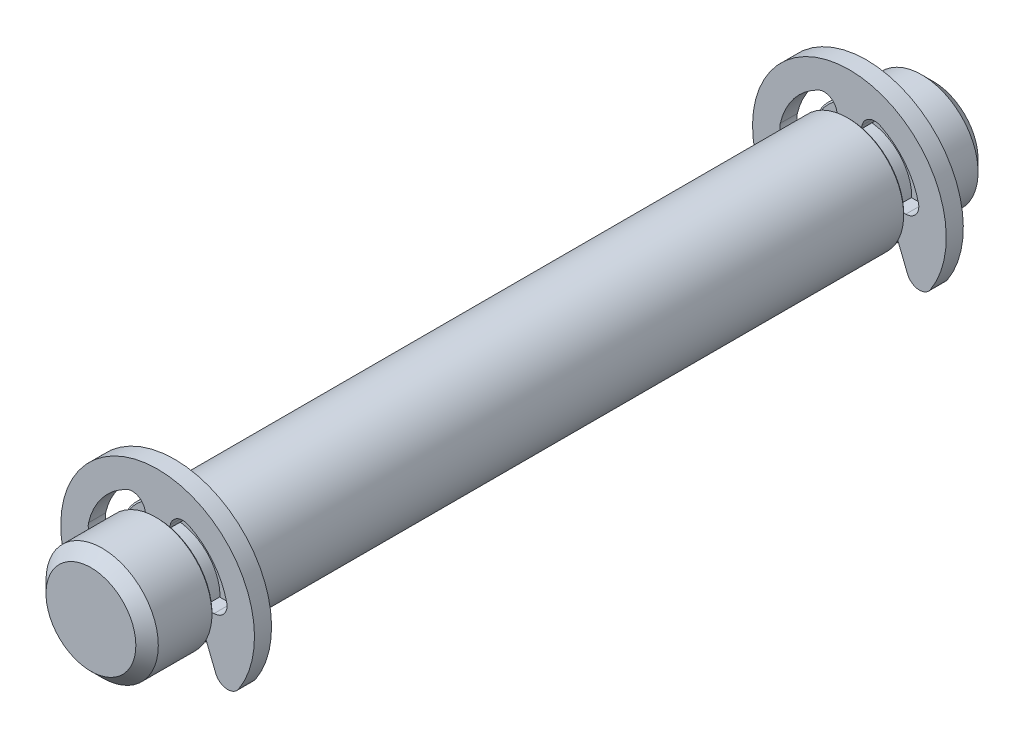
SolidWorks part; units mm, degrees
material "Plain Carbon Steel"
ref_plane "Front" through (0, 0, 0) normal (0, 0, 1) x (1, 0, 0)
ref_plane "Top" through (0, 0, 0) normal (0, 1, 0) x (1, 0, 0)
ref_plane "Right" through (0, 0, 0) normal (1, 0, 0) x (0, 0, -1)
sketch "Sketch0" plane through (0, 0, 0) normal (0, 1, 0) x (1, 0, 0)
  line L0 (0, 12) -> (0, -12) construction
  line L1 (0, -15) -> (0, 15) construction
  line L2 (-2, 0) -> (2, 0) construction
  line L3 (-1.6, 12) -> (1.6, 12) construction
  line L4 (-1.6, 12.64) -> (1.6, 12.64) construction
  point P3 (0, 0)
  point P12 (0, 0)
  point P14 (0, 12)
  point P17 (0, 0)
  point P20 (0, 12.64)
  dimension "Usable_L" = 24
  dimension "OA_L" = 30
  dimension "Pin_OD" = 4
  dimension "Groove_OD" = 3.2
  dimension "Groove_W" = 0.64
sketch "Sketch1" plane through (0, 0, 0) normal (0, 1, 0) x (1, 0, 0)
  line L1 (-2, 12) -> (-1.6, 12)
  line L2 (-1.6, 12) -> (-1.6, 12.64)
  line L3 (-1.6, 12.64) -> (-2, 12.64)
  line L4 (-2, 12.64) -> (-2, 15)
  line L5 (-2, 15) -> (0, 15)
  line L9 (-2, 0) -> (2, 0) construction
  line L10 (0, 15) -> (0, -15)
  line L11 (-2, -15) -> (0, -15)
  line L12 (-2, -12.64) -> (-2, -15)
  line L13 (-1.6, -12.64) -> (-2, -12.64)
  line L14 (-1.6, -12) -> (-1.6, -12.64)
  line L15 (-2, -12) -> (-1.6, -12)
  line L16 (-2, -12) -> (-2, 12)
revolve "Revolve1" add sketch "Sketch1" angle 360 about L10
chamfer "Chamfer1" distance 0.4 angle 45 2 edges at (-2, 0, -15) (-2, 0, 15)
ref_plane "Plane1" through (0, 0, 12.32) normal (0, 0, 1) x (1, 0, 0)
sketch "Sketch2" plane through (0, 0, 12.32) normal (0, 0, 1) x (1, 0, 0)
  line L14 (-2.3509, -2.525) -> (2.3509, -2.525) construction
  line L15 (0, 1.6) -> (0, 3.45) construction
  line L18 (-2.3509, -2.525) -> (-1.5317, -0.4625)
  line L19 (2.3509, -2.525) -> (1.5317, -0.4625)
  line L24 (1.6, 0) -> (2.525, 0) construction
  line L25 (-1.6, 0) -> (-2.0625, 0) construction
  line L26 (-2.0625, 0) -> (-2.525, 0) construction
  line L27 (0, 0) -> (0, -0.4625) construction
  line L28 (-1.5317, -0.4625) -> (1.5317, -0.4625) construction
  line L29 (-1.6, 0) -> (-2.525, 0)
  line L30 (0, 2.525) -> (0, 1.6) construction
  line L31 (-0.4507, 1.9588) -> (-0.5662, 2.4607)
  line L32 (0.4507, 1.9588) -> (0.5662, 2.4607)
  line L33 (1.6, 0) -> (2.525, 0)
  circle A25 centre (0, 0) radius 1.6 construction
  circle A26 centre (0, 0) radius 1.6 construction
  arc A27 (2.3509, -2.525) -> (-2.3509, -2.525) centre (0, 0) ccw
  circle A35 centre (0, 0) radius 2.525 construction
  arc A41 (-1.5317, -0.4625) -> (-1.6, 0) centre (0, 0) cw
  arc A42 (1.5317, -0.4625) -> (1.6, 0) centre (0, 0) ccw
  arc A43 (-0.4507, 1.9588) -> (0.4507, 1.9588) centre (0, 2.0625) ccw
  arc A44 (-2.525, 0) -> (-0.5662, 2.4607) centre (0, 0) cw
  arc A45 (0.5662, 2.4607) -> (2.525, 0) centre (0, 0) cw
  point P5 (0, 2.525)
  point P18 (0, 2.0625)
  dimension "Ret.Ring_OD" = 6.9
extrude "Boss-Extrude2" add sketch "Sketch2" along normal mid plane 0.608 separate body
sketch "Sketch3" plane through (0, 0, 12.624) normal (0, 0, 1) x (1, 0, 0)
  line L0 (0.4507, 1.9588) -> (0.5662, 2.4607) construction
  line L1 (0.4507, 1.9588) -> (0.5662, 2.4607) construction
  arc A0 (2.525, 0) -> (0.5662, 2.4607) centre (0, 0) ccw construction
  arc A1 (2.525, 0) -> (0.5662, 2.4607) centre (0, 0) ccw construction
  arc A2 (0.4507, 1.9588) -> (1.1036, 2.2711) centre (0.9014, 1.8551) cw
  dimension "D1" = 0.4625
fillet "Fillet1" radius 0.4625 6 edges at (2.525, 0, 12.32) (-0.5662, 2.4607, 12.32) (-2.525, 0, 12.32) (0.5662, 2.4607, 12.32) (2.3509, -2.525, 12.32) (-2.3509, -2.525, 12.32)
chamfer "Chamfer2" distance 0.05 angle 45 4 edges at (-2, 0, -12.64) (-2, 0, -12) (-2, 0, 12) (-2, 0, 12.64)
mirror "Mirror1" about plane through (0, 0, 0) normal (0, 0, 1) of bodies 119
ref_axis "Center Axis 1" through (0, 0, 15) along (0, 0, -1)
equation "\"D1@Chamfer1\"=(\"Pin_OD@Sketch0\"-\"Groove_OD@Sketch0\")/2"
equation "\"D1@Chamfer2\"=\"D1@Chamfer1\"/8"
equation "\"D1@Boss-Extrude2\"=\"Groove_W@Sketch0\"*0.95"
equation "\"D1@Fillet1\"=\"D1@Sketch3\""
